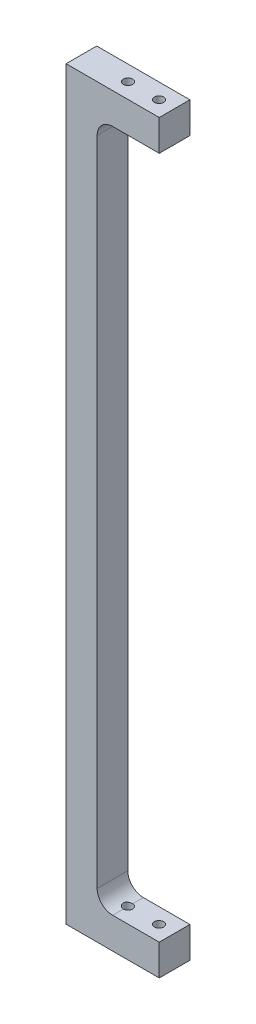
SolidWorks part; units mm, degrees
material "ABS PC"
ref_plane "Front Plane" through (0, 0, 0) normal (0, 0, 1) x (1, 0, 0)
ref_plane "Top Plane" through (0, 0, 0) normal (0, 1, 0) x (1, 0, 0)
ref_plane "Right Plane" through (0, 0, 0) normal (1, 0, 0) x (0, 0, -1)
sketch "Sketch1" plane through (0, 0, 0) normal (0, 1, 0) x (1, 0, 0)
  line L1 (-5, -4.9375) -> (5, -4.9375)
  line L2 (-5, -4.9375) -> (-5, 4.9375)
  line L3 (-5, 4.9375) -> (5, 4.9375)
  line L4 (5, -4.9375) -> (5, 4.9375)
  line L5 (-5, -4.9375) -> (5, 4.9375) construction
  line L6 (-5, 4.9375) -> (5, -4.9375) construction
  point P0 (0, 0)
  dimension "D1" = 10
  dimension "D2" = 9.875
extrude "Boss-Extrude1" add sketch "Sketch1" along normal blind 240
sketch "Sketch2" plane through (5, 0, 0) normal (1, 0, 0) x (0, 0, -1)
  line L0 (-4.9375, 240) -> (-4.9375, 0) construction
  line L1 (4.9375, 0) -> (-4.9375, 0)
  line L2 (4.9375, 0) -> (4.9375, 10)
  line L3 (4.9375, 10) -> (-4.9375, 10)
  line L4 (-4.9375, 0) -> (-4.9375, 10)
  line L6 (4.9375, 240) -> (-4.9375, 240)
  line L7 (4.9375, 240) -> (4.9375, 230)
  line L8 (4.9375, 230) -> (-4.9375, 230)
  line L9 (-4.9375, 240) -> (-4.9375, 230)
  dimension "D1" = 10
extrude "Boss-Extrude2" add sketch "Sketch2" along normal blind 20
sketch "Sketch3" plane through (0, 240, 0) normal (0, 1, 0) x (1, 0, 0)
  line L1 (25, 4.9375) -> (25, -4.9375) construction
  circle A0 centre (10, 0) radius 1.5
  circle A1 centre (20, 0) radius 1.5
  dimension "D3" = 3
  dimension "D1" = 10
  dimension "D2" = 5
extrude "Cut-Extrude1" cut sketch "Sketch3" against normal through all
fillet "Fillet1" radius 5 2 edges at (5, 230, 0) (5, 10, 0)
